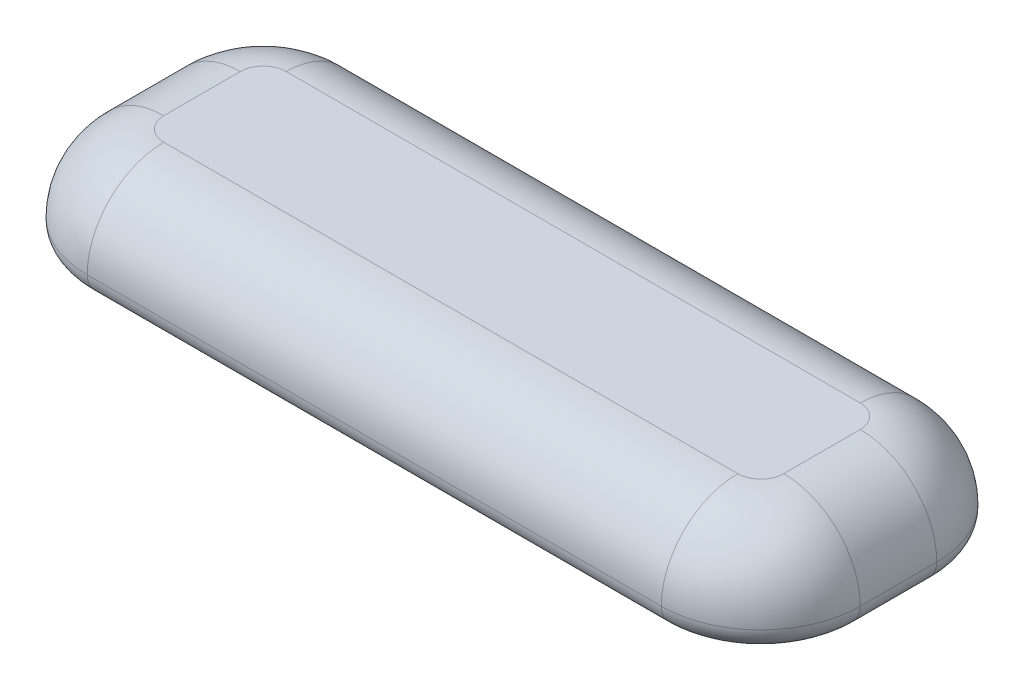
SolidWorks part; units mm, degrees
ref_plane "前视基准面" through (0, 0, 0) normal (0, 0, 1) x (1, 0, 0)
ref_plane "上视基准面" through (0, 0, 0) normal (0, 1, 0) x (1, 0, 0)
ref_plane "右视基准面" through (0, 0, 0) normal (1, 0, 0) x (0, 0, -1)
sketch "草图1" plane through (0, 0, 0) normal (0, 1, 0) x (1, 0, 0)
  line L1 (-37.5, 15) -> (37.5, 15)
  line L2 (-47.5, 5) -> (-47.5, -5)
  line L3 (-37.5, -15) -> (37.5, -15)
  line L4 (47.5, 5) -> (47.5, -5)
  line L5 (0, -15) -> (0, 15) construction
  line L6 (-47.5, 0) -> (47.5, 0) construction
  arc A0 (-47.5, -5) -> (-37.5, -15) centre (-37.5, -5) ccw
  arc A1 (-47.5, 5) -> (-37.5, 15) centre (-37.5, 5) cw
  arc A2 (37.5, 15) -> (47.5, 5) centre (37.5, 5) cw
  arc A3 (47.5, -5) -> (37.5, -15) centre (37.5, -5) cw
  point P0 (0, 0)
  point P8 (-47.5, 15)
  point P11 (47.5, 15)
  point P15 (47.5, -15)
  dimension "D3" = 10
  dimension "D1" = 95
  dimension "D2" = 30
extrude "凸台-拉伸1" add sketch "草图1" along normal blind 10
shell "抽壳2" thickness 3 removed face at (0, 0, 0) outward yes
fillet "圆角3" radius 10 8 edges at (46.6924, 13, -14.1924) (50.5, 13, 0) (46.6924, 13, 14.1924) (0, 13, 18) (-46.6924, 13, 14.1924) (-50.5, 13, 0) (-46.6924, 13, -14.1924) (0, 13, -18)
fillet "圆角4" radius 3 8 edges at (50.5, 0, 0) (46.6924, 0, 14.1924) (0, 0, 18) (-46.6924, 0, 14.1924) (-50.5, 0, 0) (-46.6924, 0, -14.1924) (0, 0, -18) (46.6924, 0, -14.1924)
ref_plane "基准面1" through (0, 10, 0) normal (0, -1, 0) x (-1, 0, 0)
sketch "草图2" plane through (0, 10, 0) normal (0, -1, 0) x (-1, 0, 0)
  line L0 (0, 0) -> (37, 0) construction
  line L1 (0, 0) -> (0, 6.5357) construction
  line L2 (34.95, 0.55) -> (39.05, 0.55)
  line L3 (34.95, 0.55) -> (34.95, -0.55)
  line L4 (34.95, -0.55) -> (39.05, -0.55)
  line L5 (39.05, 0.55) -> (39.05, -0.55)
  line L6 (37, -0.55) -> (37, 0.55) construction
  line L7 (34.95, 0) -> (39.05, 0) construction
  line L8 (36.45, 2.05) -> (37.55, 2.05)
  line L9 (36.45, 2.05) -> (36.45, -2.05)
  line L10 (36.45, -2.05) -> (37.55, -2.05)
  line L11 (37.55, 2.05) -> (37.55, -2.05)
  line L12 (37, -2.05) -> (37, 2.05) construction
  line L13 (36.45, 0) -> (37.55, 0) construction
  line L14 (-36.45, 0) -> (-37.55, 0) construction
  line L15 (-37, -2.05) -> (-37, 2.05) construction
  line L16 (-34.95, 0) -> (-39.05, 0) construction
  line L17 (-37, -0.55) -> (-37, 0.55) construction
  line L18 (-37.55, 2.05) -> (-37.55, -2.05)
  line L19 (-36.45, -2.05) -> (-37.55, -2.05)
  line L20 (-36.45, 2.05) -> (-36.45, -2.05)
  line L21 (-36.45, 2.05) -> (-37.55, 2.05)
  line L22 (-39.05, 0.55) -> (-39.05, -0.55)
  line L23 (-34.95, -0.55) -> (-39.05, -0.55)
  line L24 (-34.95, 0.55) -> (-34.95, -0.55)
  line L25 (-34.95, 0.55) -> (-39.05, 0.55)
  circle A0 centre (37, 0) radius 2.725
  circle A1 centre (-37, 0) radius 2.725
  dimension "D2" = 5.45
  dimension "D1" = 37
  dimension "D3" = 4.1
  dimension "D4" = 1.1
  dimension "D5" = 4.1
  dimension "D6" = 1.1
extrude "凸台-拉伸2" add sketch "草图2" along normal blind 8 contours A0 L8 L11 L2 L5 L4 L10 L9 L3 | A1 L25 L24 L23 L20 L19 L18 L22 L21 region at (-34.3521, 10, 0) region at (39.6479, 10, 0)
fillet "圆角7" radius 5 8 edges at (0, 10, 15) (44.5711, 10, 12.0711) (47.5, 10, 0) (44.5711, 10, -12.0711) (0, 10, -15) (-44.5711, 10, -12.0711) (-47.5, 10, 0) (-44.5711, 10, 12.0711)
chamfer "倒角1" distance 0.2 angle 45 12 edges at (37, 2, -2.05) (36.45, 2, -1.3) (35.7, 2, -0.55) (34.95, 2, 0) (35.7, 2, 0.55) (36.45, 2, 1.3) (37, 2, 2.05) (37.55, 2, 1.3) (38.3, 2, 0.55) (39.05, 2, 0) (38.3, 2, -0.55) (37.55, 2, -1.3)
chamfer "倒角2" distance 0.2 angle 45 12 edges at (-36.45, 2, -1.3) (-35.7, 2, -0.55) (-34.95, 2, 0) (-35.7, 2, 0.55) (-36.45, 2, 1.3) (-37, 2, 2.05) (-37.55, 2, 1.3) (-38.3, 2, 0.55) (-39.05, 2, 0) (-38.3, 2, -0.55) (-37.55, 2, -1.3) (-37, 2, -2.05)
fillet "圆角9" radius 4 1 edges at (37, 10, -2.725) second distance 2.5 first distance on face at (37, 2, -2.725)
fillet "圆角10" radius 2.5 1 edges at (-37, 10, 2.725) second distance 4
